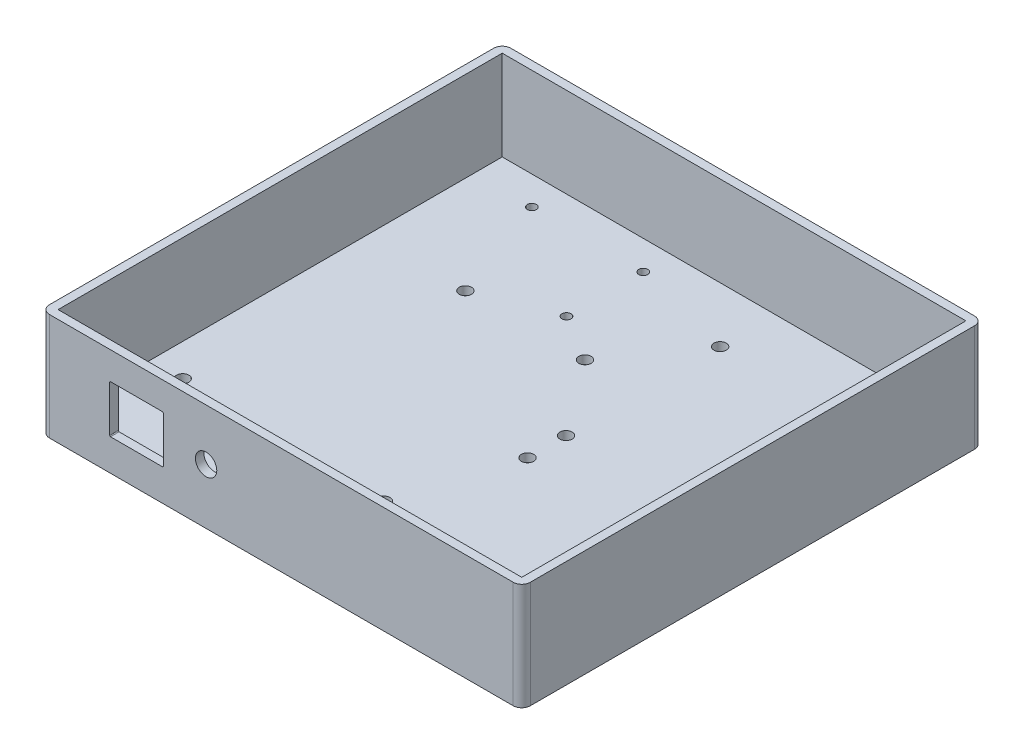
SolidWorks part; units mm, degrees
ref_plane "Front Plane" through (0, 0, 0) normal (0, 0, 1) x (1, 0, 0)
ref_plane "Top Plane" through (0, 0, 0) normal (0, 1, 0) x (1, 0, 0)
ref_plane "Right Plane" through (0, 0, 0) normal (1, 0, 0) x (0, 0, -1)
sketch "Sketch1" plane through (0, 878.6284, 0) normal (0, 1, 0) x (1, 0, 0)
  line L0 (666.5112, -1261.621) -> (666.5112, -1327.661) construction
  line L1 (661.5112, -1230.231) -> (769.8512, -1230.231)
  line L2 (661.5112, -1230.231) -> (661.5112, -1334.011)
  line L3 (661.5112, -1334.011) -> (769.8512, -1334.011)
  line L4 (769.8512, -1230.231) -> (769.8512, -1334.011)
  line L5 (666.5112, -1261.621) -> (666.5112, -1327.661)
  line L6 (666.5112, -1327.661) -> (719.8512, -1327.661) construction
  line L7 (666.5112, -1327.661) -> (719.8512, -1327.661)
  line L8 (764.8512, -1327.661) -> (764.8512, -1284.661) construction
  line L9 (708.6548, -1235.231) -> (672.3548, -1235.231) construction
  line L10 (687.3912, -1334.011) -> (676.2712, -1334.011) construction
  dimension "D2" = 5
  dimension "D1" = 5
  dimension "D3" = 5
extrude "Boss-Extrude1" add sketch "Sketch1" against normal blind 4 contours L3 L4 L1 L2
sketch "Sketch2" plane through (0, 874.6284, 0) normal (0, 1, 0) x (1, 0, 0)
  line L1 (661.5112, -1230.231) -> (659.5112, -1230.231)
  line L2 (661.5112, -1230.231) -> (661.5112, -1334.011)
  line L3 (661.5112, -1334.011) -> (659.5112, -1334.011)
  line L4 (661.5112, -1230.231) -> (661.5112, -1334.011)
  line L5 (661.5112, -1334.011) -> (769.8512, -1334.011)
  line L6 (769.8512, -1334.011) -> (769.8512, -1230.231)
  line L7 (769.8512, -1230.231) -> (661.5112, -1230.231)
  line L8 (661.5112, -1230.231) -> (661.5112, -1334.011)
  line L9 (661.5112, -1334.011) -> (769.8512, -1334.011)
  line L10 (769.8512, -1334.011) -> (769.8512, -1230.231)
  line L11 (769.8512, -1230.231) -> (661.5112, -1230.231)
  line L12 (659.5112, -1230.231) -> (659.5112, -1334.011)
  line L13 (659.5112, -1230.231) -> (769.8512, -1230.231)
  line L14 (659.5112, -1230.231) -> (659.5112, -1228.231)
  line L15 (659.5112, -1228.231) -> (769.8512, -1228.231)
  line L16 (769.8512, -1230.231) -> (769.8512, -1228.231)
  line L17 (769.8512, -1228.231) -> (771.8512, -1228.231)
  line L18 (769.8512, -1228.231) -> (769.8512, -1334.011)
  line L19 (769.8512, -1334.011) -> (771.8512, -1334.011)
  line L20 (771.8512, -1228.231) -> (771.8512, -1334.011)
  line L21 (659.5112, -1334.011) -> (771.8512, -1334.011)
  line L22 (659.5112, -1334.011) -> (659.5112, -1336.011)
  line L23 (659.5112, -1336.011) -> (771.8512, -1336.011)
  line L24 (771.8512, -1334.011) -> (771.8512, -1336.011)
  dimension "D2" = 2
extrude "Boss-Extrude2" add sketch "Sketch2" along normal blind 25 separate body contours L16 L15 L14 L1 | L1 L12 L3 | L20 L17 L16 L19 | L24 L19 L3 L22 L23 region at (660.5112, 874.6284, 1282.121) region at (714.6812, 874.6284, 1229.231) region at (715.6812, 874.6284, 1335.011) region at (770.8512, 874.6284, 1281.121)
sketch "Sketch4" plane through (0, 0, 1336.011) normal (0, 0, 1) x (1, 0, 0)
  line L0 (687.8912, 893.1684) -> (675.7712, 893.1684)
  line L1 (675.5712, 892.9684) -> (675.5712, 882.2184)
  line L2 (675.7712, 882.0184) -> (687.8912, 882.0184)
  line L3 (688.0912, 882.2184) -> (688.0912, 892.9684)
  line L4 (687.3912, 892.4684) -> (676.2712, 892.4684)
  line L5 (676.2712, 892.4684) -> (676.2712, 882.7184)
  line L6 (676.2712, 882.7184) -> (687.3912, 882.7184)
  line L7 (687.3912, 882.7184) -> (687.3912, 892.4684)
  line L8 (687.3912, 892.4684) -> (676.2712, 892.4684)
  line L9 (676.2712, 892.4684) -> (676.2712, 882.7184)
  line L10 (676.2712, 882.7184) -> (687.3912, 882.7184)
  line L11 (687.3912, 882.7184) -> (687.3912, 892.4684)
  line L12 (675.5712, 882.0184) -> (688.0912, 882.0184) construction
  line L13 (675.5712, 893.1684) -> (675.5712, 882.0184) construction
  line L14 (688.0912, 882.0184) -> (688.0912, 893.1684) construction
  line L15 (688.0912, 893.1684) -> (675.5712, 893.1684) construction
  arc A0 (675.7712, 882.0184) -> (675.5712, 882.2184) centre (675.7712, 882.2184) cw
  arc A1 (688.0912, 882.2184) -> (687.8912, 882.0184) centre (687.8912, 882.2184) cw
  arc A2 (688.0912, 892.9684) -> (687.8912, 893.1684) centre (687.8912, 892.9684) ccw
  arc A3 (675.7712, 893.1684) -> (675.5712, 892.9684) centre (675.7712, 892.9684) ccw
  dimension "D2" = 0.7
extrude "Cut-Extrude1" cut sketch "Sketch4" against normal up to surface (2 mm away) contours L10 L11 L8 L9 | L0 A3 L1 A0 L2 A1 L3 A2 L11 L10 L9 L8 region at (687.9141, 892.9913, 1336.011) region at (681.8312, 887.5934, 1336.011) up to face at (715.6812, 887.1284, 1334.011)
fillet "Fillet1" radius 2 4 edges at (659.5112, 887.1284, 1336.011) (659.5112, 887.1284, 1228.231) (771.8512, 887.1284, 1228.231) (771.8512, 887.1284, 1336.011)
sketch "Sketch5" plane through (0, 878.6284, 0) normal (0, 1, 0) x (1, 0, 0)
  circle A0 centre (761.3512, -1243.161) radius 1.75 construction
  circle A1 centre (761.3512, -1279.161) radius 1.75 construction
  circle A2 centre (725.3512, -1279.161) radius 1.75 construction
  circle A3 centre (725.3512, -1243.161) radius 1.75 construction
  circle A4 centre (761.3512, -1324.161) radius 1.75 construction
  circle A5 centre (761.3512, -1288.161) radius 1.75 construction
  circle A6 centre (725.3512, -1288.161) radius 1.75 construction
  circle A7 centre (725.3512, -1324.161) radius 1.75 construction
  circle A8 centre (669.0512, -1312.421) radius 1.5875 construction
  circle A9 centre (717.3112, -1313.691) radius 1.5875 construction
  circle A10 centre (675.1048, -1236.911) radius 1.05 construction
  circle A11 centre (701.2648, -1237.031) radius 1.05 construction
  circle A12 centre (701.2648, -1254.971) radius 1.05 construction
  circle A13 centre (712.2312, -1261.621) radius 1.5875 construction
  circle A14 centre (684.2912, -1261.621) radius 1.5875 construction
  circle A15 centre (761.3512, -1243.161) radius 1.75
  circle A16 centre (761.3512, -1279.161) radius 1.75
  circle A17 centre (725.3512, -1279.161) radius 1.75
  circle A18 centre (725.3512, -1243.161) radius 1.75
  circle A19 centre (761.3512, -1324.161) radius 1.75
  circle A20 centre (761.3512, -1288.161) radius 1.75
  circle A21 centre (725.3512, -1288.161) radius 1.75
  circle A22 centre (725.3512, -1324.161) radius 1.75
  circle A23 centre (669.0512, -1312.421) radius 1.5875
  circle A24 centre (717.3112, -1313.691) radius 1.5875
  circle A25 centre (675.1048, -1236.911) radius 1.05
  circle A26 centre (701.2648, -1237.031) radius 1.05
  circle A27 centre (701.2648, -1254.971) radius 1.05
  circle A28 centre (712.2312, -1261.621) radius 1.5875
  circle A29 centre (684.2912, -1261.621) radius 1.5875
  circle A30 centre (684.2912, -1261.621) radius 1.4375
  circle A31 centre (712.2312, -1261.621) radius 1.4375
  circle A32 centre (725.3512, -1279.161) radius 1.4375
  circle A33 centre (725.3512, -1288.161) radius 1.4375
  circle A34 centre (761.3512, -1279.161) radius 1.4375
  circle A35 centre (725.3512, -1243.161) radius 1.4375
  circle A36 centre (761.3512, -1243.161) radius 1.4375
  circle A37 centre (761.3512, -1288.161) radius 1.4375
  circle A38 centre (717.3112, -1313.691) radius 1.4375
  circle A39 centre (725.3512, -1324.161) radius 1.4375
  circle A40 centre (761.3512, -1324.161) radius 1.4375
  circle A41 centre (669.0512, -1312.421) radius 1.4375
  dimension "D1" = 0.15
extrude "Cut-Extrude2" cut sketch "Sketch5" against normal blind 2 contours A30 | A25 | A26 | A27 | A31 | A35 | A36 | A32 | A34 | A37 | A33 | A40 | A39 | A38 | A41 region at (675.1048, 878.6284, 1236.911) region at (701.2648, 878.6284, 1237.031) region at (701.2648, 878.6284, 1254.971) region at (684.2912, 878.6284, 1261.621) region at (712.2312, 878.6284, 1261.621) region at (725.3512, 878.6284, 1279.161) region at (725.3512, 878.6284, 1288.161) region at (761.3512, 878.6284, 1279.161) region at (725.3512, 878.6284, 1243.161) region at (761.3512, 878.6284, 1243.161) region at (761.3512, 878.6284, 1288.161) region at (717.3112, 878.6284, 1313.691) region at (725.3512, 878.6284, 1324.161) region at (761.3512, 878.6284, 1324.161) region at (669.0512, 878.6284, 1312.421)
sketch "Sketch6" plane through (0, 0, 1336.011) normal (0, 0, 1) x (1, 0, 0)
  line L0 (698.0912, 887.5934) -> (688.0912, 887.5934)
  line L1 (688.0912, 882.2184) -> (688.0912, 892.9684) construction
  circle A0 centre (698.0912, 887.5934) radius 2.5
  dimension "D1" = 5
  dimension "D2" = 10
extrude "Cut-Extrude3" cut sketch "Sketch6" against normal up to surface (2 mm away) contours A0 region at (698.0912, 885.1641, 1336.011) up to face at (681.8312, 887.5934, 1334.011)
equation "\"D2\"=110"
equation "\"C\"=5"
equation "\"D2@Sketch1\"=\"C\""
equation "\"D1\"=100"
equation "\"T\"= 2"
equation "\"BT\"=4"
equation "\"D1@Boss-Extrude1\"=\"BT\""
equation "\"D1@Sketch1\"=\"C\""
equation "\"D3@Sketch1\"=\"C\""
equation "\"D2@Sketch2\"=\"T\""
equation "\"H\"= 25"
equation "\"D1@Boss-Extrude2\"=\"H\""
equation "\"CS\"=0.7"
equation "\"D2@Sketch4\"=\"CS\""
equation "\"F\"=0.2"
equation "\"D3@Sketch4\"=\"F\""
equation "\"F2\"=2"
equation "\"D1@Fillet1\"=\"F2\""
equation "\"D\"=2"
equation "\"D1@Cut-Extrude2\"=\"D\""
equation "\"HOLED\"=5"
equation "\"D1@Sketch6\"=\"HOLED\""
equation "\"CSS\"=0.15"
equation "\"D1@Sketch5\"=\"CSS\""
